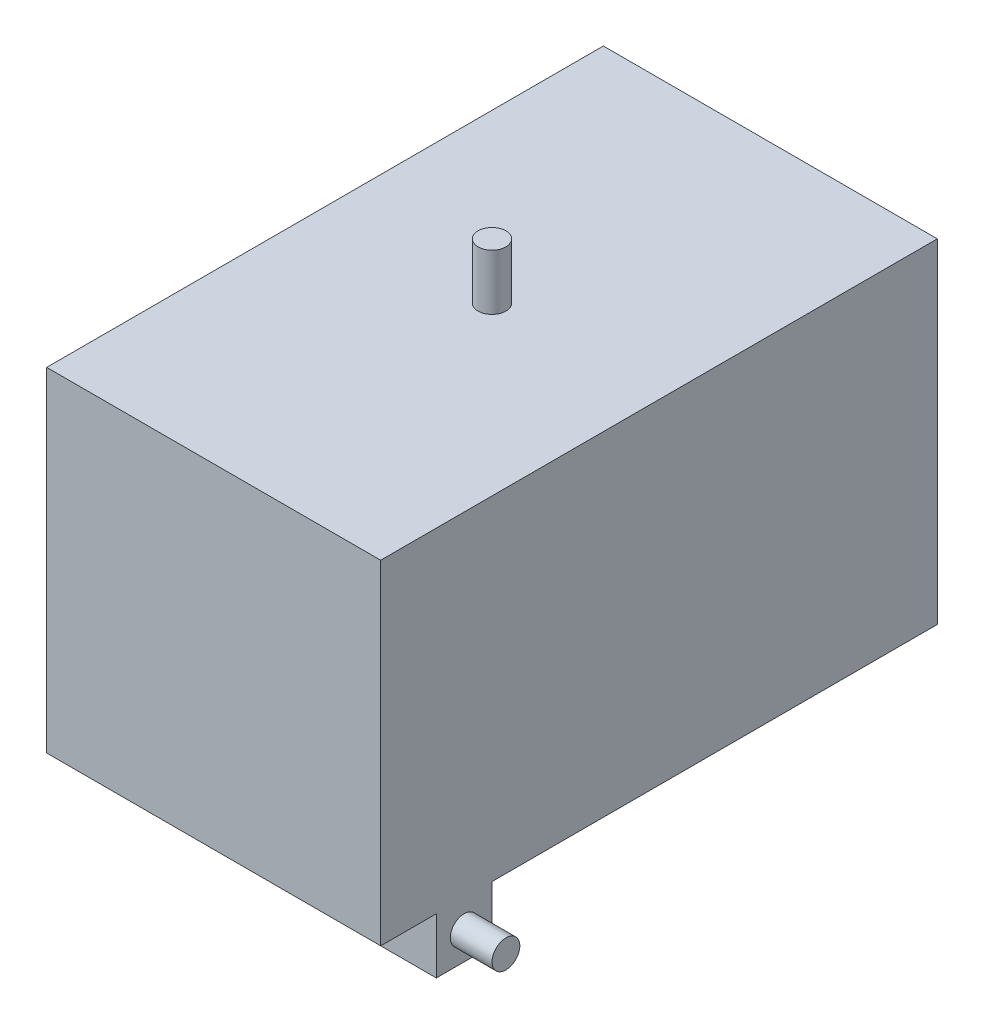
SolidWorks part; units mm, degrees
material "6061-T6 (SS)"
ref_plane "Front Plane" through (0, 0, 0) normal (0, 0, 1) x (1, 0, 0)
ref_plane "Top Plane" through (0, 0, 0) normal (0, 1, 0) x (1, 0, 0)
ref_plane "Right Plane" through (0, 0, 0) normal (1, 0, 0) x (0, 0, -1)
sketch "Sketch1" plane through (0, 0, 0) normal (0, 0, 1) x (1, 0, 0)
  line L1 (-73.025, -73.025) -> (73.025, -73.025)
  line L2 (-73.025, -73.025) -> (-73.025, 73.025)
  line L3 (-73.025, 73.025) -> (73.025, 73.025)
  line L4 (73.025, -73.025) -> (73.025, 73.025)
  line L5 (-73.025, -73.025) -> (73.025, 73.025) construction
  line L6 (-73.025, 73.025) -> (73.025, -73.025) construction
  line L7 (-76.2, -76.2) -> (76.2, -76.2)
  line L8 (-76.2, -76.2) -> (-76.2, 76.2)
  line L9 (-76.2, 76.2) -> (76.2, 76.2)
  line L10 (76.2, -76.2) -> (76.2, 76.2)
  line L11 (-76.2, -76.2) -> (76.2, 76.2) construction
  line L12 (-76.2, 76.2) -> (76.2, -76.2) construction
  point P0 (0, 0)
  point P6 (0, 0)
  dimension "D1" = 3.175
  dimension "D2" = 3.175
  dimension "D3" = 152.4
extrude "Boss-Extrude1" add sketch "Sketch1" along normal mid plane 254
sketch "Sketch2" plane through (0, 0, 127) normal (0, 0, 1) x (1, 0, 0)
  line L1 (-73.025, -73.025) -> (73.025, -73.025)
  line L2 (-73.025, -73.025) -> (-73.025, 73.025)
  line L3 (-73.025, 73.025) -> (73.025, 73.025)
  line L4 (73.025, -73.025) -> (73.025, 73.025)
  line L5 (-73.025, -73.025) -> (73.025, 73.025) construction
  line L6 (-73.025, 73.025) -> (73.025, -73.025) construction
  point P0 (0, 0)
extrude "Boss-Extrude2" add sketch "Sketch2" against normal blind 3.175
sketch "Sketch3" plane through (0, 0, -127) normal (0, 0, -1) x (-1, 0, 0)
  line L1 (-73.025, -73.025) -> (73.025, -73.025)
  line L2 (-73.025, -73.025) -> (-73.025, 73.025)
  line L3 (-73.025, 73.025) -> (73.025, 73.025)
  line L4 (73.025, -73.025) -> (73.025, 73.025)
  line L5 (-73.025, -73.025) -> (73.025, 73.025) construction
  line L6 (-73.025, 73.025) -> (73.025, -73.025) construction
  point P0 (0, 0)
extrude "Boss-Extrude3" add sketch "Sketch3" against normal blind 3.175
sketch "Sketch4" plane through (0, -76.2, 0) normal (0, -1, 0) x (1, 0, 0)
  line L0 (0, -1000) -> (0, 49000) construction
  line L1 (76.2, 127) -> (76.2, -127) construction
  line L2 (25.4, 101.6) -> (76.2, 101.6)
  line L3 (25.4, 101.6) -> (25.4, 76.2)
  line L4 (25.4, 76.2) -> (76.2, 76.2)
  line L5 (76.2, 101.6) -> (76.2, 76.2)
  line L6 (25.4, 101.6) -> (76.2, 76.2) construction
  line L7 (25.4, 76.2) -> (76.2, 101.6) construction
  line L8 (-76.2, 127) -> (76.2, 127) construction
  line L9 (-25.4, 76.2) -> (-76.2, 101.6) construction
  line L10 (-25.4, 101.6) -> (-76.2, 76.2) construction
  line L11 (-76.2, 101.6) -> (-76.2, 76.2)
  line L12 (-25.4, 76.2) -> (-76.2, 76.2)
  line L13 (-25.4, 101.6) -> (-25.4, 76.2)
  line L14 (-25.4, 101.6) -> (-76.2, 101.6)
  point P1 (50.8, 88.9)
  point P16 (-50.8, 88.9)
  dimension "D1" = 25.4
  dimension "D2" = 25.4
  dimension "D3" = 50.8
extrude "Boss-Extrude4" add sketch "Sketch4" along normal blind 25.4 separate body
ref_plane "Plane1" through (0, 0, -101.6) normal (0, 0, -1) x (-1, 0, 0)
sketch "Sketch6" plane through (0, 0, -101.6) normal (0, 0, -1) x (-1, 0, 0)
  line L0 (0, -76.2) -> (0, -127)
  line L4 (76.2, -76.2) -> (-76.2, -76.2) construction
  line L5 (25.4, -101.6) -> (9.525, -101.6)
  line L6 (9.525, -101.6) -> (9.525, -76.2)
  line L7 (9.525, -76.2) -> (0, -76.2)
  line L8 (76.2, -101.6) -> (25.4, -101.6) construction
  arc A0 (0, -127) -> (25.4, -101.6) centre (0, -101.6) ccw
  dimension "D1" = 9.525
  dimension "D2" = 50.8
revolve "Revolve2" add sketch "Sketch6" angle 360 about L0
sketch "Sketch7" plane through (0, 76.2, 0) normal (0, 1, 0) x (1, 0, 0)
  line L0 (0, 127) -> (0, -127) construction
  line L1 (76.2, -127) -> (-76.2, -127) construction
  line L2 (76.2, 0) -> (-76.2, 0) construction
  line L3 (76.2, -127) -> (76.2, 127) construction
  line L4 (-76.2, -127) -> (-76.2, 127) construction
  line L5 (76.2, 127) -> (-76.2, 127) construction
  circle A0 centre (0, 0) radius 6.35
  dimension "D1" = 12.7
extrude "Boss-Extrude5" add sketch "Sketch7" along normal blind 25.4
sketch "Sketch8" plane through (76.2, 0, 0) normal (1, 0, 0) x (0, 0, -1)
  line L0 (-88.9, -101.6) -> (-88.9, -76.2) construction
  line L1 (-76.2, -101.6) -> (-101.6, -101.6) construction
  line L2 (-76.2, -76.2) -> (-101.6, -76.2) construction
  circle A0 centre (-88.9, -88.9) radius 6.35
  dimension "D1" = 12.7
extrude "Boss-Extrude6" add sketch "Sketch8" along normal blind 19.05
sketch "Sketch9" plane through (-76.2, 0, 0) normal (-1, 0, 0) x (0, 0, 1)
  line L0 (88.9, -101.6) -> (88.9, -76.2) construction
  line L1 (101.6, -101.6) -> (76.2, -101.6) construction
  line L2 (101.6, -76.2) -> (76.2, -76.2) construction
  circle A0 centre (88.9, -88.9) radius 6.35
  dimension "D1" = 12.7
extrude "Boss-Extrude7" add sketch "Sketch9" along normal blind 19.05
